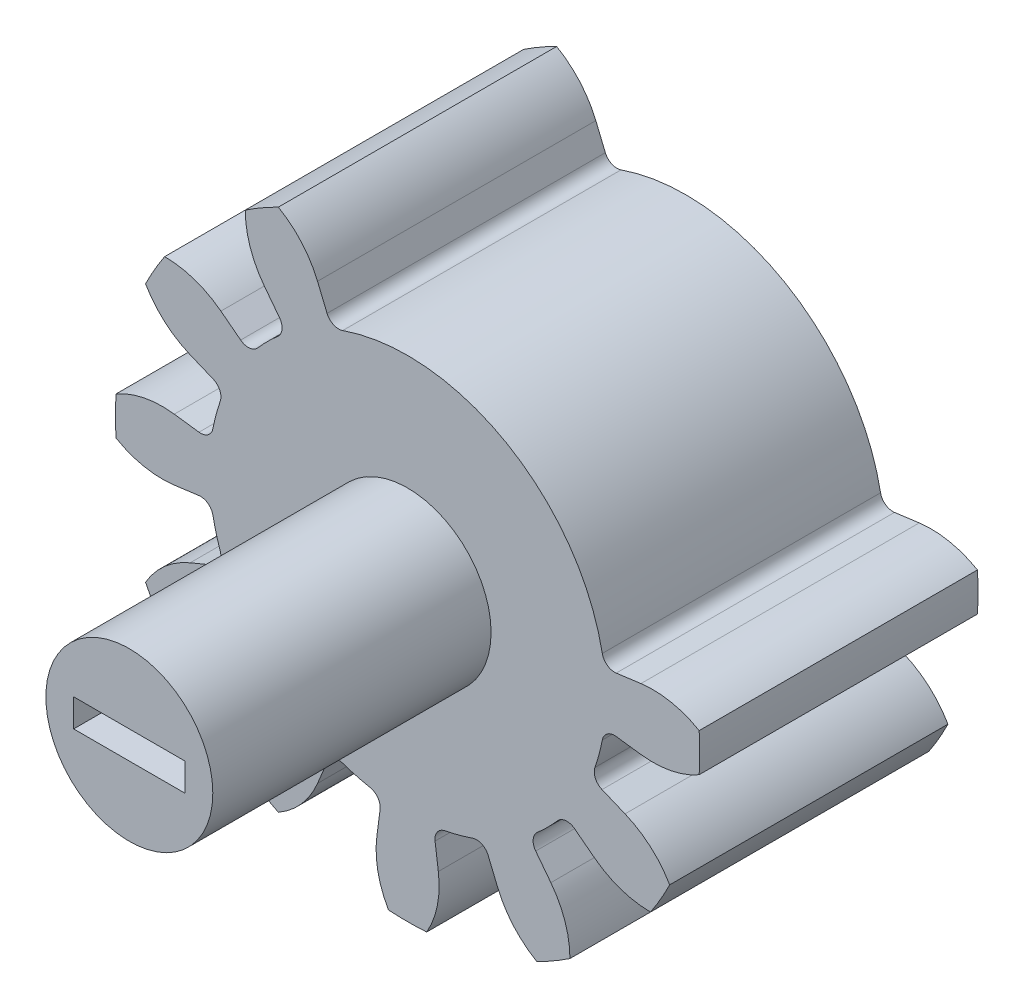
SolidWorks part; units mm, degrees
ref_plane "Front Plane" through (0, 0, 0) normal (0, 0, 1) x (1, 0, 0)
ref_plane "Top Plane" through (0, 0, 0) normal (0, 1, 0) x (1, 0, 0)
ref_plane "Right Plane" through (0, 0, 0) normal (1, 0, 0) x (0, 0, -1)
sketch "Esquisse1" plane through (0, 0, 0) normal (0, 0, 1) x (1, 0, 0)
  line L0 (0, 0) -> (22.1157, 0) construction
  line L1 (0, 0) -> (24.1492, 6.4708) construction
  line L2 (0, 0) -> (24.1492, -6.4708) construction
  line L3 (0, 0) -> (24.9429, 3.2838) construction
  line L4 (0, 0) -> (6.8822, 1.8441)
  line L5 (0, 0) -> (19.7164, -2.5957) construction
  line L6 (0, 0) -> (6.8822, -1.8441)
  line L7 (0, 0) -> (17.7915, 1.1661) construction
  line L8 (7.064, 0.93) -> (8.3849, 1.1039)
  line L9 (7.064, -0.93) -> (8.3849, -1.1039)
  line L10 (0, 0) -> (17.695, -1.1598) construction
  circle A0 centre (0, 0) radius 9 construction
  circle A1 centre (0, 0) radius 10.5 construction
  circle A2 centre (0, 0) radius 7.125 construction
  circle A3 centre (0, 0) radius 8.4572 construction
  arc A4 (6.8822, 1.8441) -> (7.064, 0.93) centre (0, 0) cw
  arc A5 (6.8822, -1.8441) -> (7.064, -0.93) centre (0, 0) ccw
  arc A6 (8.3849, 1.1039) -> (10.4775, 0.6867) centre (8.8176, -2.1828) cw
  arc A7 (10.4775, 0.6867) -> (10.4775, -0.6867) centre (0, 0) cw
  arc A8 (8.3849, -1.1039) -> (10.4775, -0.6867) centre (8.8176, 2.1828) ccw
  dimension "PrimitiveDiameter" = 18
  dimension "OutsideDiameter" = 21
  dimension "InternalDiameter" = 14.25
  dimension "BaseDiameter" = 16.9145
  dimension "DemiToothAngle" = 15
  dimension "QuartToothAngle" = 7.5
  dimension "D1" = 7.5
  dimension "D2" = 3.75
  dimension "D3" = 3.75
extrude "Boss.-Extru.2" add sketch "Esquisse1" along normal blind 10
fillet "Congé1" radius 0.45 2 edges at (7.064, -0.93, 5) (7.064, 0.93, 5)
ref_axis "Axe1" through (0, 0, 10) along (0, 0, -1)
pattern_circular "Répétition circulaire1" count 9 every 30 about axis through (0, 0, 10) along (0, 0, -1) of "Boss.-Extru.2", "Congé1"
sketch "Esquisse3" plane through (0, 0, 10) normal (0, 0, 1) x (1, 0, 0)
  circle A0 centre (0, 0) radius 3
  dimension "D1" = 6
extrude "Boss.-Extru.3" add sketch "Esquisse3" along normal blind 10
sketch "Esquisse5" plane through (0, 0, 10) normal (0, 0, 1) x (1, 0, 0)
  circle A0 centre (0, 0) radius 7.125
  arc A3 (-1.8441, 6.8822) -> (-2.3308, 6.733) centre (0, 0) ccw construction
extrude "Boss.-Extru.4" add sketch "Esquisse5" against normal through all
sketch "Esquisse4" plane through (0, 0, 20) normal (0, 0, 1) x (1, 0, 0)
  line L1 (-2, 0.5) -> (2, 0.5)
  line L2 (-2, 0.5) -> (-2, -0.5)
  line L3 (-2, -0.5) -> (2, -0.5)
  line L4 (2, 0.5) -> (2, -0.5)
  point P5 (0, -0.5)
  point P7 (-2, 0)
  dimension "D1" = 4
  dimension "D2" = 1
extrude "Enlèv. mat.-Extru.1" cut sketch "Esquisse4" against normal blind 3
equation "\"Modulo\"= 1.5mm"
equation "\"ToothCount\"= 12"
equation "\"PrimitiveDiameter@Esquisse1\"= \"Modulo\" * \"ToothCount\""
equation "\"OutsideDiameter@Esquisse1\" = \"Modulo\" *  ( \"ToothCount\" + 2 ) "
equation "\"InternalDiameter@Esquisse1\" = \"PrimitiveDiameter@Esquisse1\" - \"Modulo\" * 2.5"
equation "\"Angle\"= 20deg"
equation "\"BaseDiameter@Esquisse1\" = \"PrimitiveDiameter@Esquisse1\" * cos ( \"Angle\" ) "
equation "\"DemiToothAngle@Esquisse1\" = 180 / \"ToothCount\""
equation "\"QuartToothAngle@Esquisse1\"= \"DemiToothAngle@Esquisse1\" / 2"
equation "\"D1@Esquisse1\"= \"QuartToothAngle@Esquisse1\""
equation "\"D2@Esquisse1\"= \"QuartToothAngle@Esquisse1\" / 2"
equation "\"D3@Esquisse1\"= \"D2@Esquisse1\""
equation "\"D2@Répétition circulaire1\"=360/\"ToothCount\""
equation "\"D1@Congé1\"=\"Modulo\"*0.3"
